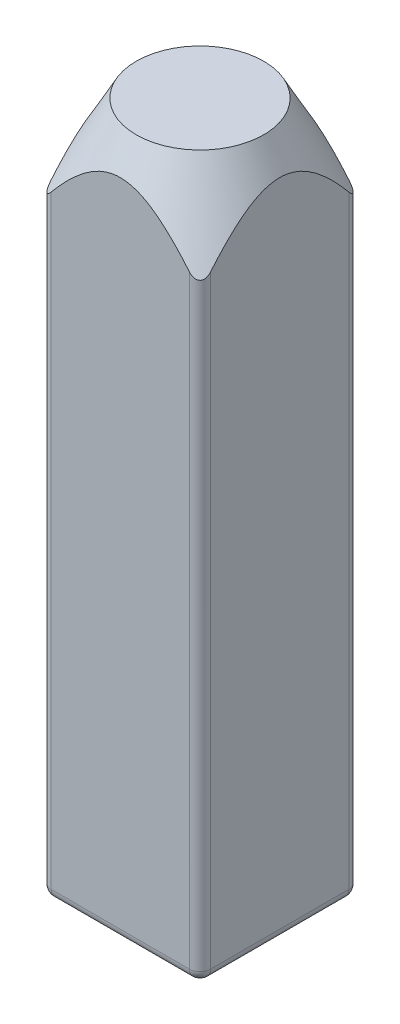
SolidWorks part; units mm, degrees
ref_plane "Front Plane" through (0, 0, 0) normal (0, 0, 1) x (1, 0, 0)
ref_plane "Top Plane" through (0, 0, 0) normal (0, 1, 0) x (1, 0, 0)
ref_plane "Right Plane" through (0, 0, 0) normal (1, 0, 0) x (0, 0, -1)
sketch "Sketch1" plane through (0, 0, 0) normal (0, 1, 0) x (1, 0, 0)
  line L1 (-7.5, -7.5) -> (7.5, -7.5)
  line L2 (-7.5, -7.5) -> (-7.5, 7.5)
  line L3 (-7.5, 7.5) -> (7.5, 7.5)
  line L4 (7.5, -7.5) -> (7.5, 7.5)
  point P6 (0, -7.5)
  point P8 (-7.5, 0)
  dimension "D1" = 15
extrude "Boss-Extrude1" add sketch "Sketch1" along normal blind 65
ref_axis "Axis1" through (0, 73.5, 0) along (0, -1, 0)
sketch "Sketch2" plane through (0, 0, 0) normal (0, 0, 1) x (1, 0, 0)
  line L0 (-7.5, 65) -> (7.5, 65) construction
  line L3 (6, 65) -> (10.9848, 55.9034)
  line L4 (0, 73.5) -> (0, -3.5) construction
  line L6 (10.9848, 55.9034) -> (10.9848, 65)
  line L7 (10.9848, 65) -> (6, 65)
  dimension "D1" = 6
revolve "Cut-Revolve4" cut sketch "Sketch2" angle 360 about axis through (0, 73.5, 0) along (0, -1, 0)
fillet "Fillet1" radius 1 4 edges at (-7.5, 28.2968, -7.5) (7.5, 28.2968, -7.5) (7.5, 28.2968, 7.5) (-7.5, 28.2968, 7.5)
fillet "Fillet2" radius 1 8 edges at (-7.2071, 0, 7.2071) (-7.5, 0, 0) (-7.2071, 0, -7.2071) (0, 0, -7.5) (7.2071, 0, -7.2071) (7.5, 0, 0) (7.2071, 0, 7.2071) (0, 0, 7.5)
